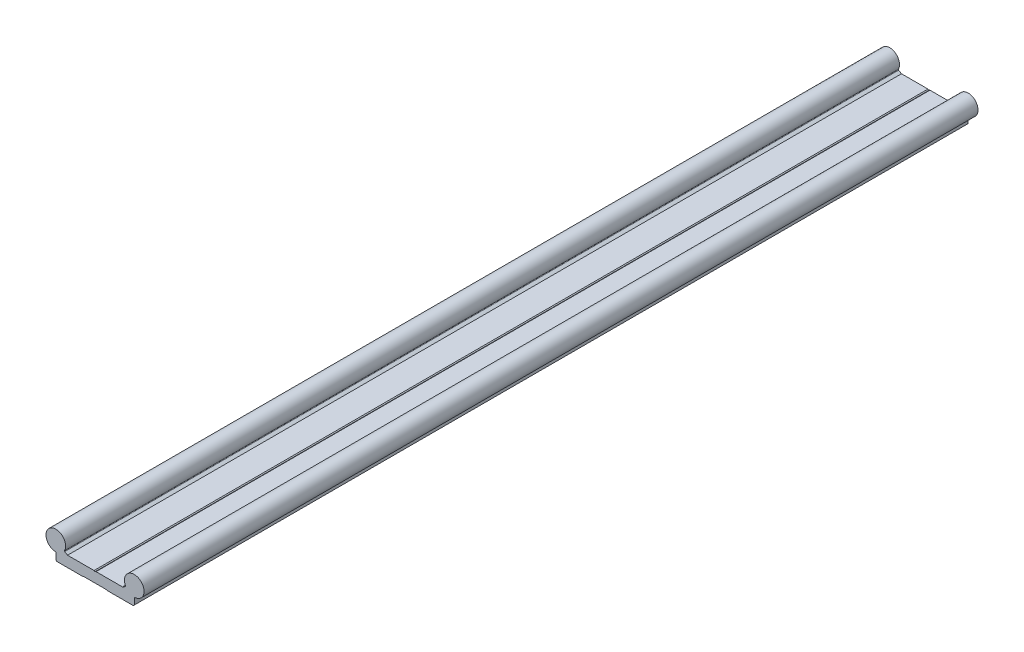
SolidWorks part; units mm, degrees
material "6061 Alloy"
ref_plane "Front Plane" through (0, 0, 0) normal (0, 0, 1) x (1, 0, 0)
ref_plane "Top Plane" through (0, 0, 0) normal (0, 1, 0) x (1, 0, 0)
ref_plane "Right Plane" through (0, 0, 0) normal (1, 0, 0) x (0, 0, -1)
ref_plane "Plane1" through (0, 0, 425) normal (0, 0, 1) x (1, 0, 0)
sketch "Sketch1" plane through (0, 0, 425) normal (0, 0, 1) x (1, 0, 0)
  line L0 (-20, 0.5) -> (-19.5, 0)
  line L1 (-19.5, 0) -> (-6, 0)
  line L2 (-6, 0) -> (-5.8, 0.2)
  line L3 (-5.8, 0.2) -> (5.8, 0.2)
  line L4 (5.8, 0.2) -> (6, 0)
  line L5 (6, 0) -> (19.5, 0)
  line L6 (19.5, 0) -> (20, 0.5)
  line L7 (20, 0.5) -> (20, 3.7085)
  line L8 (15.4315, 6.3265) -> (14, 5.5)
  line L9 (14, 5.5) -> (0.5, 5.5)
  line L10 (0.5, 5.5) -> (0, 5.2113)
  line L11 (0, 5.2113) -> (-0.5, 5.5)
  line L12 (-0.5, 5.5) -> (-14, 5.5)
  line L13 (-14, 5.5) -> (-15.4315, 6.3265)
  line L14 (-20, 3.7085) -> (-20, 0.5)
  arc A0 (20, 3.7085) -> (20.283, 4.008) centre (20.3, 3.7085) cw
  arc A1 (20.283, 4.008) -> (15.5486, 6.7229) centre (20, 9) ccw
  arc A2 (15.5486, 6.7229) -> (15.4315, 6.3265) centre (15.2815, 6.5863) cw
  arc A3 (-15.4315, 6.3265) -> (-15.5486, 6.7229) centre (-15.2815, 6.5863) cw
  arc A4 (-15.5486, 6.7229) -> (-20.283, 4.008) centre (-20, 9) ccw
  arc A5 (-20.283, 4.008) -> (-20, 3.7085) centre (-20.3, 3.7085) cw
extrude "Boss-Extrude1" add sketch "Sketch1" against normal blind 425
ref_axis "Axis1" through (20, 9, 0) along (0, 0, 1)
ref_axis "Axis2" through (-20, 9, 0) along (0, 0, 1)
